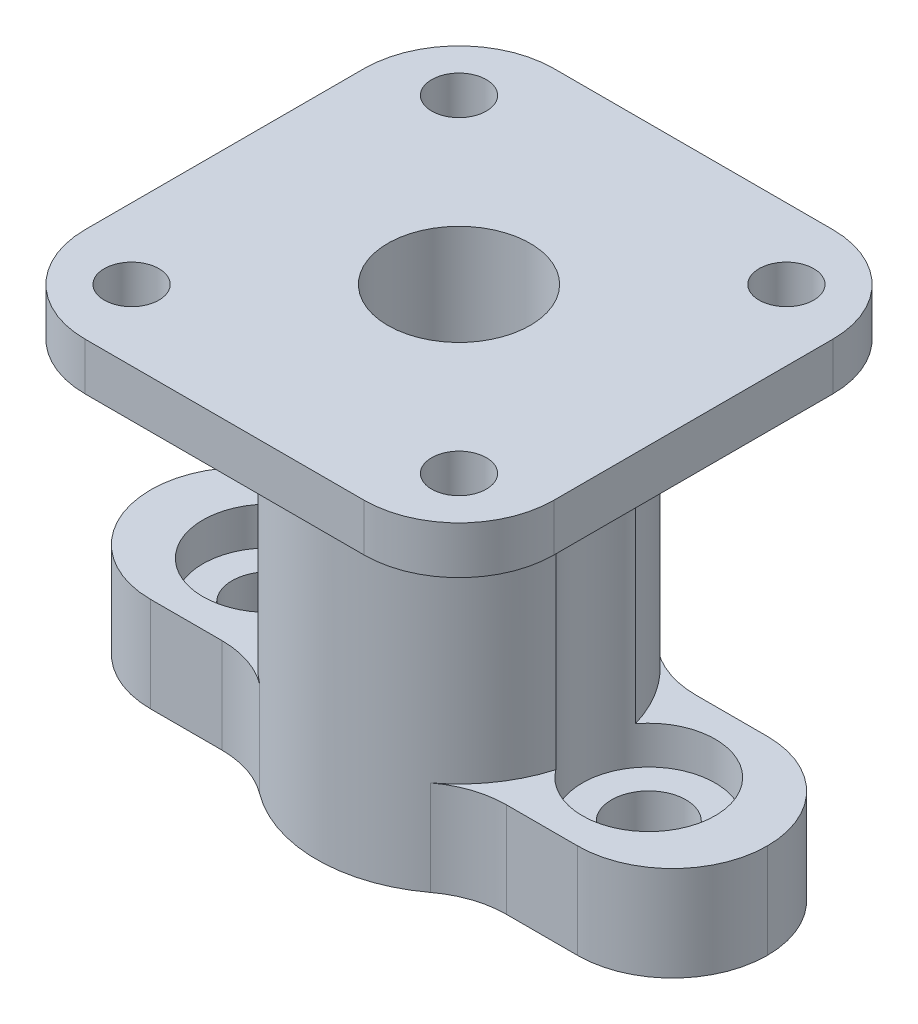
SolidWorks part; units mm, degrees
ref_plane "Front" through (0, 0, 0) normal (0, 0, 1) x (1, 0, 0)
ref_plane "Top" through (0, 0, 0) normal (0, 1, 0) x (1, 0, 0)
ref_plane "Right" through (0, 0, 0) normal (1, 0, 0) x (0, 0, -1)
sketch "Sketch8" plane through (0, 0, 0) normal (0, 1, 0) x (1, 0, 0)
  line L1 (20.6375, -6.35) -> (-20.6375, -6.35)
  line L2 (20.6375, -6.35) -> (20.6375, 6.35)
  line L3 (20.6375, 6.35) -> (-20.6375, 6.35)
  line L4 (-20.6375, -6.35) -> (-20.6375, 6.35)
  line L5 (20.6375, -6.35) -> (-20.6375, 6.35) construction
  line L6 (20.6375, 6.35) -> (-20.6375, -6.35) construction
  circle A0 centre (0, 0) radius 9.525
  point P0 (0, 0)
  dimension "D2" = 19.05
  dimension "D1" = 41.275
  dimension "D3" = 12.7
extrude "Boss-Extrude2" add sketch "Sketch8" along normal blind 6.35 contours A0 L3 L4 L1 | L1 A0 L3 | A0 L1 L2 L3 | A0 region at (14.6791, 0, 0) region at (0, 0, 0) region at (-14.6791, 0, 0)
sketch "Sketch11" plane through (0, 0, 0) normal (0, 1, 0) x (1, 0, 0)
  circle A0 centre (0, 0) radius 9.525
  arc A1 (-7.0995, -6.35) -> (7.0995, -6.35) centre (0, 0) ccw construction
extrude "Boss-Extrude3" add sketch "Sketch11" along normal blind 25.4
sketch "Sketch12" plane through (0, 25.4, 0) normal (0, 1, 0) x (1, 0, 0)
  line L1 (15.6845, -15.6845) -> (-15.6845, -15.6845)
  line L2 (15.6845, -15.6845) -> (15.6845, 15.6845)
  line L3 (15.6845, 15.6845) -> (-15.6845, 15.6845)
  line L4 (-15.6845, -15.6845) -> (-15.6845, 15.6845)
  line L5 (15.6845, -15.6845) -> (-15.6845, 15.6845) construction
  line L6 (15.6845, 15.6845) -> (-15.6845, -15.6845) construction
  point P0 (0, 0)
  dimension "D1" = 31.369
extrude "Boss-Extrude4" add sketch "Sketch12" along normal blind 3.175
sketch "Sketch13" plane through (0, 28.575, 0) normal (0, 1, 0) x (1, 0, 0)
  line L1 (10.9559, -10.9559) -> (-10.9559, -10.9559) construction
  line L2 (10.9559, -10.9559) -> (10.9559, 10.9559) construction
  line L3 (10.9559, 10.9559) -> (-10.9559, 10.9559) construction
  line L4 (-10.9559, -10.9559) -> (-10.9559, 10.9559) construction
  line L5 (10.9559, -10.9559) -> (-10.9559, 10.9559) construction
  line L6 (10.9559, 10.9559) -> (-10.9559, -10.9559) construction
  circle A0 centre (-10.9559, 10.9559) radius 1.8288
  circle A1 centre (10.9559, 10.9559) radius 1.8288
  circle A2 centre (10.9559, -10.9559) radius 1.8288
  circle A3 centre (-10.9559, -10.9559) radius 1.8288
  point P0 (0, 0)
  dimension "D1" = 3.6576
  dimension "D2" = 30.988
extrude "Cut-Extrude4" cut sketch "Sketch13" against normal up to next
sketch "Sketch14" plane through (0, 28.575, 0) normal (0, 1, 0) x (1, 0, 0)
  circle A0 centre (0, 0) radius 4.7625
  dimension "D1" = 9.525
extrude "Cut-Extrude5" cut sketch "Sketch14" against normal through all
hole_wizard "CBORE for #00 Binding Head Machine Screw1" positions "3DSketch2" profile "Sketch9" counterbore size "#00" standard "ANSI Inch" end condition through all
sketch3d "3DSketch2"
  line L0 (-12.7, 6.35, 0) -> (12.7, 6.35, 0) construction
  point P0 (-12.7, 6.35, 0)
  point P2 (12.7, 6.35, 0)
  point P11 (0, 6.35, 0)
  dimension "D1" = 25.4
sketch "Sketch9" plane through (-12.7, 6.35, 0) normal (1, 0, 0) x (0, 0, 1)
  line L0 (0, 0) -> (0, 6.35)
  line L1 (0, 6.35) -> (2.4892, 6.35)
  line L3 (2.4892, 6.35) -> (2.4892, 2.54)
  line L4 (2.4892, 2.54) -> (4.445, 2.54)
  line L5 (4.445, 2.54) -> (4.445, 0)
  line L7 (4.445, 0) -> (0, 0)
  line L11 (0, -6.35) -> (0, 107.95) construction
  dimension "Thru Hole Dia." = 4.9784
  dimension "Thru Hole Depth" = 6.35
  dimension "C'Bore Dia." = 8.89
  dimension "C'Bore Depth" = 2.54
fillet "Fillet1" radius 6.35 4 edges at (15.6845, 26.9875, 15.6845) (15.6845, 26.9875, -15.6845) (-15.6845, 26.9875, -15.6845) (-15.6845, 26.9875, 15.6845)
fillet "Fillet2" radius 6.35 8 edges at (-20.6375, 3.175, 6.35) (-20.6375, 3.175, -6.35) (20.6375, 3.175, 6.35) (20.6375, 3.175, -6.35) (-7.0995, 3.175, -6.35) (7.0995, 3.175, -6.35) (7.0995, 3.175, 6.35) (-7.0995, 3.175, 6.35)
sketch "Sketch15" plane through (0, 6.35, 0) normal (0, 1, 0) x (1, 0, 0)
  circle A0 centre (12.7, 0) radius 4.445 construction
  circle A1 centre (-12.7, 0) radius 4.445 construction
  circle A2 centre (12.7, 0) radius 4.445
  circle A3 centre (-12.7, 0) radius 4.445
extrude "Cut-Extrude6" cut sketch "Sketch15" along normal up to surface (19.05 mm away) up to face at (-10.9559, 25.4, 12.7847)
chamfer "Chamfer1" distance 3.175 angle 45 4 edges at (8.255, 25.4, 0) (0, 25.4, -9.525) (-8.255, 25.4, 0) (0, 25.4, 9.525)
fillet "Fillet4" radius 0.3175 4 edges at (0, 22.225, 9.525) (0, 25.4, 12.7) (0, 25.4, -12.7) (0, 22.225, -9.525)
